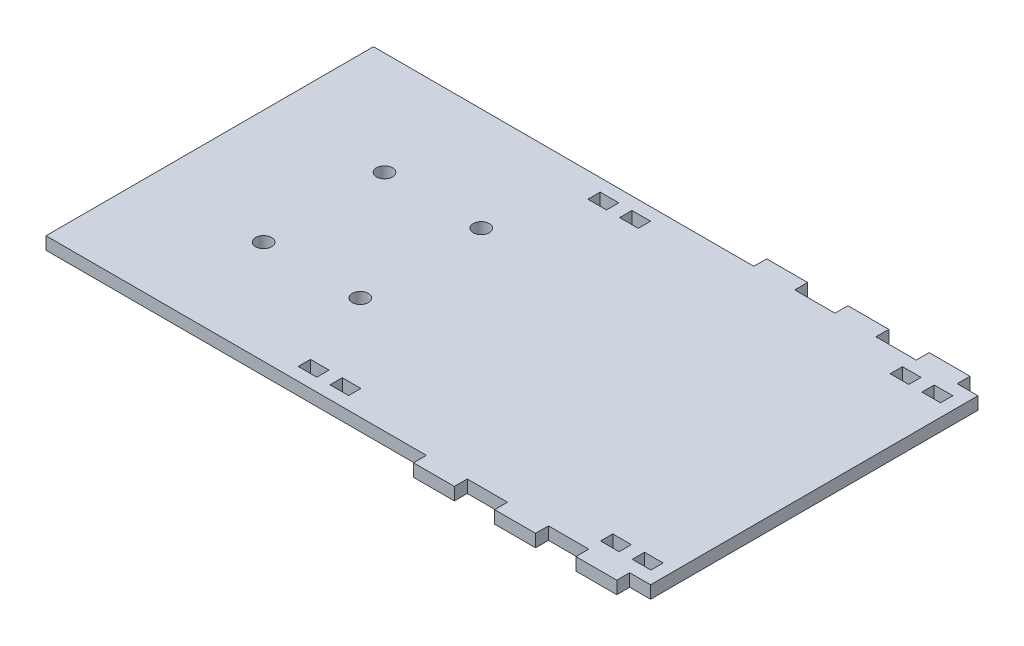
SolidWorks part; units mm, degrees
ref_plane "Front Plane" through (0, 0, 0) normal (0, 0, 1) x (1, 0, 0)
ref_plane "Top Plane" through (0, 0, 0) normal (0, 1, 0) x (1, 0, 0)
ref_plane "Right Plane" through (0, 0, 0) normal (1, 0, 0) x (0, 0, -1)
sketch "Sketch1" plane through (0, 0, 0) normal (0, 1, 0) x (1, 0, 0)
  line L0 (40.1574, -41.275) -> (50.4698, -41.275)
  line L1 (76.2, -41.275) -> (-76.2, -41.275)
  line L2 (76.2, -41.275) -> (76.2, 41.275)
  line L3 (76.2, 41.275) -> (-76.2, 41.275)
  line L4 (-76.2, -41.275) -> (-76.2, 41.275)
  line L5 (76.2, -41.275) -> (-76.2, 41.275) construction
  line L6 (76.2, 41.275) -> (-76.2, -41.275) construction
  line L7 (60.6298, -41.275) -> (70.9422, -41.275)
  line L8 (60.6298, -41.275) -> (60.6298, -44.5262)
  line L9 (60.6298, -44.5262) -> (70.9422, -44.5262)
  line L10 (70.9422, -41.275) -> (70.9422, -44.5262)
  line L11 (40.1574, -41.275) -> (40.1574, -44.5262)
  line L12 (40.1574, -44.5262) -> (50.4698, -44.5262)
  line L13 (50.4698, -41.275) -> (50.4698, -44.5262)
  line L14 (19.685, -41.275) -> (29.9974, -41.275)
  line L15 (19.685, -41.275) -> (19.685, -44.5262)
  line L16 (19.685, -44.5262) -> (29.9974, -44.5262)
  line L17 (29.9974, -41.275) -> (29.9974, -44.5262)
  line L18 (60.6298, 44.5262) -> (70.9422, 44.5262)
  line L19 (60.6298, 44.5262) -> (60.6298, 41.275)
  line L20 (60.6298, 41.275) -> (70.9422, 41.275)
  line L21 (70.9422, 44.5262) -> (70.9422, 41.275)
  line L22 (40.1574, 44.5262) -> (50.4698, 44.5262)
  line L23 (40.1574, 44.5262) -> (40.1574, 41.275)
  line L24 (40.1574, 41.275) -> (50.4698, 41.275)
  line L25 (50.4698, 44.5262) -> (50.4698, 41.275)
  line L26 (19.685, 44.5262) -> (29.9974, 44.5262)
  line L27 (19.685, 44.5262) -> (19.685, 41.275)
  line L28 (19.685, 41.275) -> (29.9974, 41.275)
  line L29 (29.9974, 44.5262) -> (29.9974, 41.275)
  point P0 (0, 0)
  point P10 (60.6298, -42.9006)
  dimension "D1" = 3.2512
  dimension "D2" = 10.3124
  dimension "D5" = 10.16
  dimension "D6" = 82.55
  dimension "D7" = 152.4
  dimension "D8" = 5.2578
  dimension "D3" = 3
  dimension "D4" = 2
extrude "Boss-Extrude1" add sketch "Sketch1" along normal blind 3.175 contours L17 L1 L15 L16 | L4 L1 L0 L2 L3 | L13 L0 L11 L12 | L29 L26 L27 L3 | L10 L9 L8 L7 | L18 L21 L20 L19 | L22 L25 L24 L23 region at (0, 0, 0) region at (45.3136, 0, 42.9006) region at (24.8412, 0, 42.9006) region at (24.8412, 0, -42.9006)
sketch "Sketch2" plane through (0, 3.175, 0) normal (0, 1, 0) x (1, 0, 0)
  line L0 (-47.3754, 15.24) -> (-47.3754, -15.24) construction
  line L1 (-47.3754, 0) -> (-76.2, 0) construction
  line L2 (-76.2, -41.275) -> (-76.2, 41.275) construction
  circle A0 centre (-47.3754, 15.24) radius 2.0193
  circle A1 centre (-22.9914, 15.24) radius 2.0193
  circle A2 centre (-22.9914, -15.24) radius 2.0193
  circle A3 centre (-47.3754, -15.24) radius 2.0193
  dimension "D4" = 24.384
  dimension "D5" = 4.0386
  dimension "D3" = 30.48
  dimension "D1" = 2
  dimension "D2" = 2
extrude "Caster Mounting Holes" cut sketch "Sketch2" against normal through all
sketch "Sketch3" plane through (0, 3.175, 0) normal (0, 1, 0) x (1, 0, 0)
  line L2 (65.0113, 38.1) -> (65.0113, 35.0012)
  line L4 (68.3387, 38.1) -> (68.3387, 35.0012)
  line L5 (60.6298, 41.275) -> (50.4698, 41.275) construction
  line L7 (76.2, -41.275) -> (76.2, 41.275) construction
  line L9 (68.3387, 38.1) -> (73.025, 38.1)
  line L10 (73.025, 38.1) -> (73.025, 35.0012)
  line L11 (73.025, 35.0012) -> (68.3387, 35.0012)
  line L15 (65.0113, 35.0012) -> (60.325, 35.0012)
  line L16 (60.325, 35.0012) -> (60.325, 38.1)
  line L17 (60.325, 38.1) -> (65.0113, 38.1)
  point P0 (66.675, 36.5125)
  dimension "D1" = 3.0988
  dimension "D2" = 4.6863
  dimension "D3" = 3.175
  dimension "D4" = 3.175
  dimension "D5" = 3.3274
extrude "Cut-Extrude1" cut sketch "Sketch3" against normal through all contours L17 L16 L15 L2 | L11 L10 L9 L4 region at (62.6682, 3.175, -36.5506) region at (70.6818, 3.175, -36.5506)
pattern_linear "LPattern1" count 2 spacing 76.2 along (-1, 0, 0) count 2 spacing 73.025 along (0, 0, 1) of "Cut-Extrude1"
